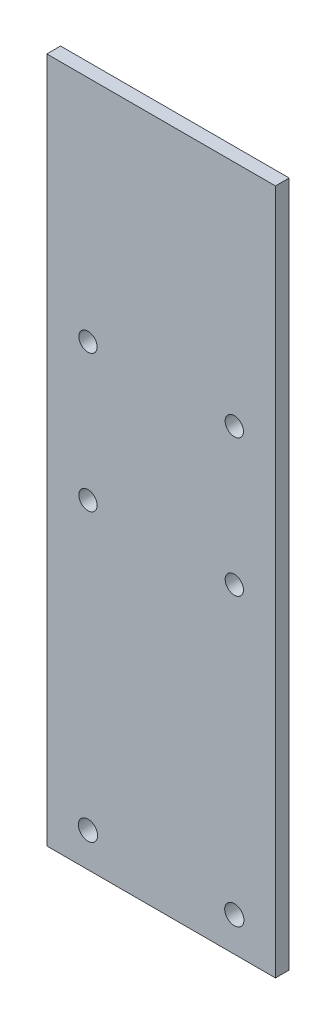
SolidWorks part; units mm, degrees
material "Plain Carbon Steel"
ref_plane "Front" through (0, 0, 0) normal (0, 0, 1) x (1, 0, 0)
ref_plane "Top" through (0, 0, 0) normal (0, 1, 0) x (1, 0, 0)
ref_plane "Right" through (0, 0, 0) normal (1, 0, 0) x (0, 0, -1)
ref_plane "Plane1" through (0, 0, 0) normal (0, 0, 1) x (1, 0, 0)
ref_axis "Axis1" through (0, 0, 0) along (0, 0, 1)
ref_plane "Plane2" through (0, 0, 0) normal (0, 1, 0) x (0, 0, 1)
ref_plane "Plane3" through (0, 0, 0) normal (-1, 0, 0) x (0, 0, 1)
sketch "Sketch1" plane through (0, 0, 0) normal (0, 0, 1) x (1, 0, 0)
  line L0 (0, 177.8933) -> (0, 0) construction
  line L1 (0, 0) -> (50, 0) construction
  line L11 (-25, -150) -> (25, -150)
  line L16 (-25, -150) -> (-25, 0)
  line L17 (-25, 0) -> (25, 0)
  line L18 (25, -150) -> (25, 0)
  point P10 (0, 0)
  dimension "D1" = 150
  dimension "D2" = 50
extrude "Boss-Extrude1" add sketch "Sketch1" along normal blind 3
sketch "Sketch2" plane through (0, 0, 0) normal (0, 0, 1) x (1, 0, 0)
  line L0 (0, 0) -> (0, -50) construction
  line L1 (0, -50) -> (-16, -50) construction
  line L2 (-16, -50) -> (-16, -80) construction
  line L3 (-16, -80) -> (16, -80) construction
  line L4 (16, -80) -> (16, -50) construction
  line L5 (16, -50) -> (0, -50) construction
  line L6 (25, 0) -> (-25, 0) construction
  line L7 (-16, -50) -> (-16, -54) construction
  line L8 (-14, -50) -> (-14, -54) construction
  line L9 (-18, -50) -> (-18, -54) construction
  line L10 (16, -50) -> (16, -54) construction
  line L11 (18, -50) -> (18, -54) construction
  line L12 (14, -50) -> (14, -54) construction
  line L13 (16, -80) -> (16, -76) construction
  line L14 (14, -80) -> (14, -76) construction
  line L15 (18, -80) -> (18, -76) construction
  line L16 (-16, -80) -> (-16, -76) construction
  line L17 (-18, -80) -> (-18, -76) construction
  line L18 (-14, -80) -> (-14, -76) construction
  arc A0 (-14, -50) -> (-18, -50) centre (-16, -50) ccw construction
  arc A1 (-18, -54) -> (-14, -54) centre (-16, -54) ccw construction
  arc A2 (18, -50) -> (14, -50) centre (16, -50) ccw construction
  arc A3 (14, -54) -> (18, -54) centre (16, -54) ccw construction
  arc A4 (14, -80) -> (18, -80) centre (16, -80) ccw construction
  arc A5 (18, -76) -> (14, -76) centre (16, -76) ccw construction
  arc A6 (-18, -80) -> (-14, -80) centre (-16, -80) ccw construction
  arc A7 (-14, -76) -> (-18, -76) centre (-16, -76) ccw construction
  circle A8 centre (-16, -50) radius 2
  circle A9 centre (16, -50) radius 2
  circle A10 centre (-16, -80) radius 2
  circle A11 centre (16, -80) radius 2
  point P9 (-16, -52)
  point P15 (16, -52)
  point P21 (16, -78)
  point P27 (-16, -78)
  dimension "D4" = 2
  dimension "D6" = 4
  dimension "D1" = 32
  dimension "D2" = 30
  dimension "D3" = 50
  dimension "D5" = 4
extrude "Cut-Extrude2" cut sketch "Sketch2" along normal through all
sketch "Sketch3" plane through (0, 0, 0) normal (0, 0, 1) x (1, 0, 0)
  line L0 (0, -150) -> (0, -142.5) construction
  line L1 (-25, -150) -> (25, -150) construction
  line L2 (0, -142.5) -> (-16, -142.5) construction
  line L3 (0, -142.5) -> (16, -142.5) construction
  circle A0 centre (-16, -142.5) radius 2.1
  circle A1 centre (16, -142.5) radius 2.1
  dimension "D1" = 32
  dimension "D2" = 4.2
  dimension "D3" = 7.5
extrude "Cut-Extrude4" cut sketch "Sketch3" along normal through all
